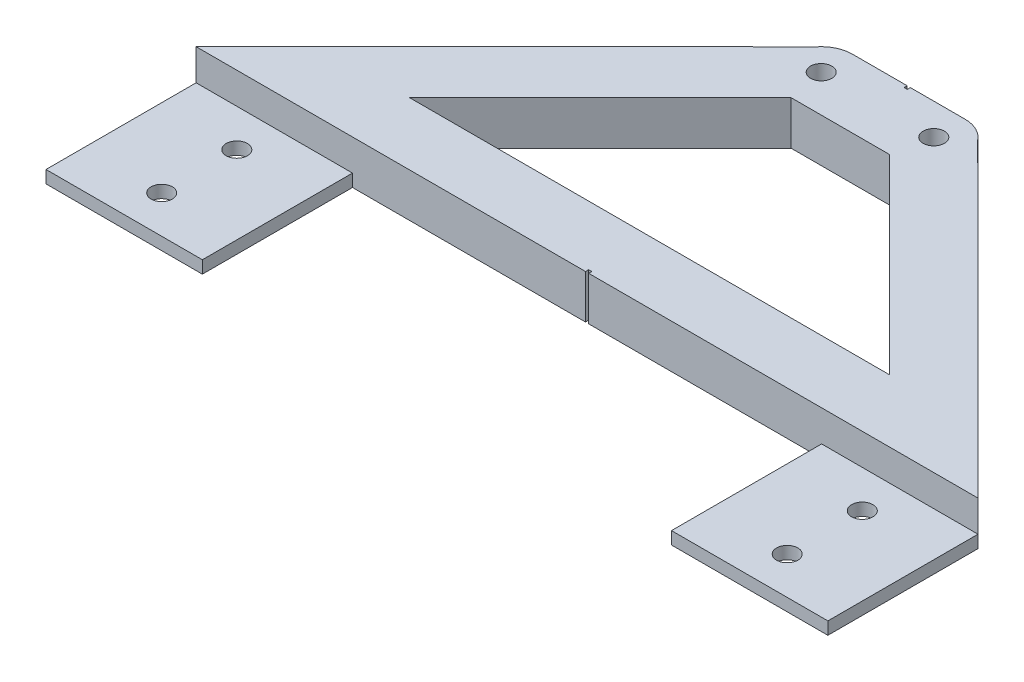
SolidWorks part; units mm, degrees
ref_plane "Front Plane" through (0, 0, 0) normal (0, 0, 1) x (1, 0, 0)
ref_plane "Top Plane" through (0, 0, 0) normal (0, 1, 0) x (1, 0, 0)
ref_plane "Right Plane" through (0, 0, 0) normal (1, 0, 0) x (0, 0, -1)
sketch "Triangle" plane through (0, 0, 0) normal (0, 1, 0) x (1, 0, 0)
  line L0 (0, 0) -> (125, 0)
  line L1 (125, 0) -> (82.5, 42.5)
  line L2 (42.5, 42.5) -> (0, 0)
  line L3 (62.5, 0) -> (62.5, 42.5) construction
  line L4 (82.5, 42.5) -> (42.5, 42.5)
  line L5 (24.1421, 10) -> (100.8579, 10)
  line L6 (100.8579, 10) -> (70.3579, 40.5)
  line L7 (70.3579, 40.5) -> (54.6421, 40.5)
  line L8 (54.6421, 40.5) -> (24.1421, 10)
  dimension "D1" = 125
  dimension "D2" = 40
  dimension "D3" = 45
  dimension "D4" = 45
  dimension "D5" = 10
  dimension "D6" = 2
  dimension "D7" = 10
  dimension "D8" = 45
  dimension "D9" = 10
  dimension "D10" = 45
sketch "Bearing Mounts" plane through (0, 0, 0) normal (0, 1, 0) x (1, 0, 0)
  line L0 (12.5, -24) -> (12.5, 0) construction
  line L1 (25, 0) -> (0, 0)
  line L2 (25, 0) -> (25, -24)
  line L3 (25, -24) -> (0, -24)
  line L4 (0, 0) -> (0, -24)
  line L5 (112.5, -24) -> (112.5, 0) construction
  line L6 (125, 0) -> (100, 0)
  line L7 (125, 0) -> (125, -24)
  line L8 (125, -24) -> (100, -24)
  line L9 (100, 0) -> (100, -24)
  line L10 (100, -24) -> (25, -24) construction
  line L11 (62.5, -24) -> (62.5, 68.4083) construction
  line L14 (62.5, 42.5) -> (62.5, -51.9511) construction
  dimension "D1" = 24
  dimension "D2" = 25
  dimension "D3" = 24
  dimension "D4" = 25
  dimension "D5" = 100
extrude "Bearing Mount Plates" add sketch "Bearing Mounts" along normal blind 2
extrude "Bridge" add sketch "Triangle" along normal blind 7
sketch "M3 Bearing Holes" plane through (0, 0, 0) normal (0, -1, 0) x (1, 0, 0)
  line L0 (125, 24) -> (125, 0) construction
  line L2 (125, 0) -> (82.5, -42.5) construction
  line L4 (100, 0) -> (100, 24) construction
  line L5 (0, 24) -> (25, 24) construction
  line L6 (0, 0) -> (125, 0) construction
  line L7 (25, 24) -> (25, 0) construction
  line L12 (100, 24) -> (125, 24) construction
  circle A0 centre (112.5, 6) radius 1.7
  circle A1 centre (112.5, 18) radius 1.7
  circle A2 centre (12.5, 6) radius 1.7
  circle A3 centre (12.5, 18) radius 1.7
  dimension "D1" = 3.4
  dimension "D5" = 6
  dimension "D10" = 3.4
  dimension "D2" = 6
  dimension "D3" = 12.5
  dimension "D4" = 6
  dimension "D6" = 12.5
  dimension "D7" = 12.5
  dimension "D8" = 6
  dimension "D9" = 12.5
extrude "Bearing Mount Holes" cut sketch "M3 Bearing Holes" against normal up to surface (2 mm away) up to face at (12.5, 2, 12)
sketch "Belt Mount" plane through (0, 0, 0) normal (0, -1, 0) x (1, 0, 0)
  line L1 (53.5, -41.4289) -> (71.5, -41.4289)
  line L2 (42.5, -42.5) -> (0, 0) construction
  line L3 (53.5, -51.4289) -> (71.5, -51.4289)
  line L4 (125, 0) -> (82.5, -42.5) construction
  arc A0 (53.5, -41.4289) -> (53.5, -51.4289) centre (53.5, -46.4289) ccw
  arc A1 (71.5, -51.4289) -> (71.5, -41.4289) centre (71.5, -46.4289) ccw
  dimension "D2" = 5
  dimension "D1" = 18
extrude "Belt Mount Plate" add sketch "Belt Mount" against normal blind 7
sketch "M3 Belt Holes" plane through (0, 0, 0) normal (0, -1, 0) x (1, 0, 0)
  circle A0 centre (53.5, -46.4289) radius 1.7
  circle A1 centre (71.5, -46.4289) radius 1.7
  dimension "D1" = 3.4
extrude "Belt Mount Screw Holes" cut sketch "M3 Belt Holes" against normal up to surface (7 mm away) up to face at (62.5, 7, -34.3824)
sketch "Sketch6" plane through (0, 0, 0) normal (0, -1, 0) x (1, 0, 0)
  line L0 (42.5, -42.5) -> (49.5, -49.4289)
  line L1 (49.5, -49.4289) -> (50.4075, -42.5)
  line L2 (50.4075, -42.5) -> (42.5, -42.5)
  line L3 (82.5, -42.5) -> (75.5, -49.4289)
  line L4 (75.5, -49.4289) -> (74.5925, -42.5)
  line L5 (74.5925, -42.5) -> (82.5, -42.5)
  line L6 (53.5, -49.4289) -> (94.0576, -49.4289) construction
  line L7 (94.0576, -49.4289) -> (23.5138, -49.4289) construction
  line L9 (53.5, -51.4289) -> (71.5, -51.4289) construction
  arc A0 (53.5, -41.4289) -> (53.5, -51.4289) centre (53.5, -46.4289) ccw construction
  arc A3 (71.5, -51.4289) -> (71.5, -41.4289) centre (71.5, -46.4289) ccw construction
  dimension "D1" = 2
extrude "Boss-Extrude1" add sketch "Sketch6" against normal up to surface (7 mm away) up to face at (71.5, 7, -48.1289)
sketch "Sketch7" plane through (0, 0, 0) normal (0, 0, 1) x (1, 0, 0)
  line L0 (62.5, 0) -> (62.5, 7)
  line L1 (0, 7) -> (125, 7) construction
  line L2 (24.1421, 0) -> (100.8579, 0) construction
  line L3 (62.25, 7) -> (62.75, 7)
  line L4 (62.25, 7) -> (62.25, 0)
  line L5 (62.25, 0) -> (62.75, 0)
  line L6 (62.75, 7) -> (62.75, 0)
  dimension "D1" = 0.25
  dimension "D2" = 0.25
extrude "Alignment helper 1" cut sketch "Sketch7" against normal blind 0.5 contours L4 L5 L6 L3
sketch "Sketch8" plane through (0, 0, -51.4289) normal (0, 0, -1) x (-1, 0, 0)
  line L0 (-62.5, 7) -> (-62.5, 0) construction
  line L1 (-53.5, 7) -> (-71.5, 7) construction
  line L2 (-53.5, 0) -> (-71.5, 0) construction
  line L4 (-62.25, 0) -> (-62.75, 0)
  line L5 (-62.25, 0) -> (-62.25, 7)
  line L6 (-62.25, 7) -> (-62.75, 7)
  line L7 (-62.75, 0) -> (-62.75, 7)
  dimension "D1" = 0.25
  dimension "D2" = 0.25
extrude "Alignment helper 2" cut sketch "Sketch8" against normal blind 0.5
